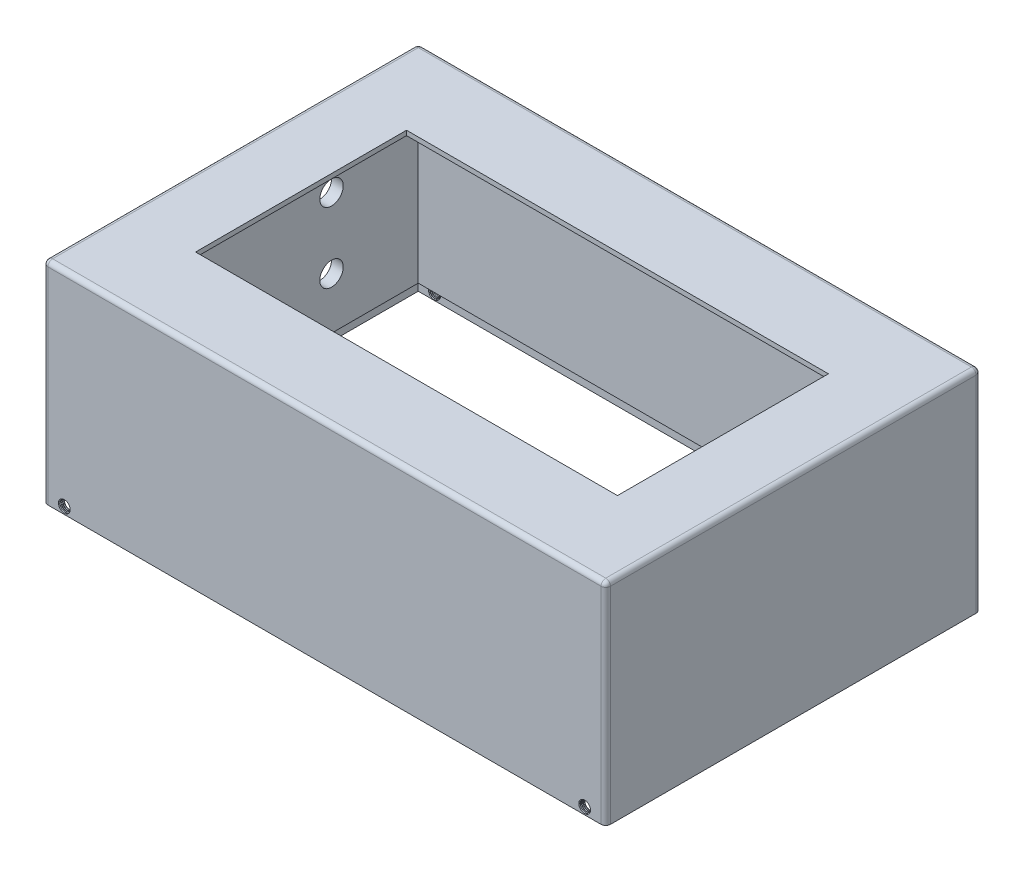
SolidWorks part; units mm, degrees
ref_plane "Front Plane" through (0, 0, 0) normal (0, 0, 1) x (1, 0, 0)
ref_plane "Top Plane" through (0, 0, 0) normal (0, 1, 0) x (1, 0, 0)
ref_plane "Right Plane" through (0, 0, 0) normal (1, 0, 0) x (0, 0, -1)
sketch "Sketch2" plane through (0, 0, 0) normal (0, 1, 0) x (1, 0, 0)
  line L1 (-60, -40) -> (60, -40)
  line L2 (-60, -40) -> (-60, 40)
  line L3 (-60, 40) -> (60, 40)
  line L4 (60, -40) -> (60, 40)
  line L5 (-60, -40) -> (60, 40) construction
  line L6 (-60, 40) -> (60, -40) construction
  point P0 (0, 0)
  dimension "D1" = 80
  dimension "D2" = 120
extrude "Boss-Extrude1" add sketch "Sketch2" along normal blind 50
sketch "Sketch3" plane through (0, 0, 0) normal (0, 1, 0) x (1, 0, 0)
  line L0 (60, -40) -> (60, 40) construction
  line L1 (-57.5, -37.2563) -> (57.5, -37.2563)
  line L2 (-57.5, -37.2563) -> (-57.5, 37.5)
  line L3 (-57.5, 37.5) -> (57.5, 37.5)
  line L4 (57.5, -37.2563) -> (57.5, 37.5)
  line L5 (-60, 40) -> (-60, -40) construction
  line L6 (60, 40) -> (-60, 40) construction
  line L7 (-60, -40) -> (60, -40) construction
  point P0 (0, 0)
  dimension "D1" = 2.5
  dimension "D2" = 2.5
  dimension "D3" = 2.5
  dimension "D4" = 2.7437
extrude "Cut-Extrude4" cut sketch "Sketch3" along normal blind 47.5
fillet "Fillet1" radius 1 8 edges at (-60, 25, -40) (60, 25, -40) (-60, 25, 40) (60, 25, 40) (60, 50, 0) (0, 50, 40) (0, 50, -40) (-60, 50, 0)
sketch "Sketch7" plane through (0, 0, -40) normal (0, 0, -1) x (-1, 0, 0)
  line L0 (-51.5, 10) -> (48.5, 10) construction
  line L1 (-59, 0) -> (59, 0) construction
  line L2 (-59, 49) -> (-59, 0) construction
  text T0 "SIMPLE SOLAR PHONE CHARGER" font "Century Gothic" height in points 18
  dimension "D1" = 10
  dimension "D2" = 100
  dimension "D3" = 7.5
extrude "Boss-Extrude2" add sketch "Sketch7" along normal blind 0.5
sketch "Sketch8" plane through (-60, 0, 0) normal (-1, 0, 0) x (0, 0, 1)
  line L0 (-39, 15) -> (39, 15) construction
  line L1 (-39, 49) -> (-39, 0) construction
  line L2 (39, 0) -> (39, 49) construction
  line L3 (-39, 0) -> (39, 0) construction
  line L4 (39, 49) -> (-39, 49) construction
  line L5 (-44.4082, 26.5) -> (-11.972, 26.5) construction
  line L6 (-10.6538, 11.5) -> (-44.4082, 11.5) construction
  circle A0 centre (-19, 34) radius 2.5
  circle A1 centre (-19, 19) radius 2.5
  text T0 "CHARGING" font "Century Gothic" height in points 8
  text T1 "FULLY CHARGED" font "Century Gothic" height in points 8
  point P19 (-19.3103, 26.5)
  point P20 (0, 0)
  point P21 (-16.5639, 26.5)
  point P22 (0, 0)
  point P23 (0, 0)
  point P24 (0, 0)
  point P25 (-16.5639, 26.5)
  point P26 (0, 0)
  point P27 (0, 0)
  dimension "D2" = 5
  dimension "D3" = 5
  dimension "D4" = 15
  dimension "D7" = 7.5
  dimension "D8" = 20
  dimension "D9" = 20
  dimension "D1" = 15
  dimension "D6" = 7.5
extrude "Cut-Extrude5" cut sketch "Sketch8" against normal blind 2.5 contours A0 | A1
sketch "Sketch9" plane through (-60, 0, 0) normal (-1, 0, 0) x (0, 0, 1)
  line L0 (-39, 28) -> (3.7538, 28) construction
  line L1 (-39, 49) -> (-39, 0) construction
  line L2 (-39, 13) -> (6, 13) construction
  circle A1 centre (-19, 34) radius 2.5 construction
  circle A2 centre (-19, 19) radius 2.5 construction
  text T0 "CHARGING" font "Century Gothic" height in points 8
  text T1 "FULLY CHARGED" font "Century Gothic" height in points 8
  point P7 (0, 0)
  point P8 (0, 0)
  point P9 (-16.6737, 27.1422)
  point P11 (0, 0)
  point P12 (0, 0)
  point P13 (-16.6737, 11.7621)
  point P14 (-3.9898, 27.2439)
  point P15 (3.7538, 27.2439)
  point P16 (-8.6536, 11.7621)
  point P17 (-7.9496, 12.3726)
  point P18 (-6.0137, 11.7621)
  point P19 (1.1139, 11.7621)
  point P20 (0, 0)
  dimension "D1" = 6
  dimension "D2" = 6
  dimension "D3" = 45
  dimension "D4" = 42.7538
extrude "Boss-Extrude3" add sketch "Sketch9" along normal blind 0.5
sketch "Sketch11" plane through (0, 50, 0) normal (0, 1, 0) x (1, 0, 0)
  line L1 (-45, -22.5) -> (45, -22.5)
  line L2 (-45, -22.5) -> (-45, 22.5)
  line L3 (-45, 22.5) -> (45, 22.5)
  line L4 (45, -22.5) -> (45, 22.5)
  line L5 (-45, -22.5) -> (45, 22.5) construction
  line L6 (-45, 22.5) -> (45, -22.5) construction
  point P0 (0, 0)
  dimension "D1" = 90
  dimension "D2" = 45
extrude "Cut-Extrude6" cut sketch "Sketch11" against normal blind 2.5
sketch "Sketch12" plane through (0, 47.5, 0) normal (0, -1, 0) x (1, 0, 0)
  line L0 (-45, 22.5) -> (45, 22.5) construction
  line L1 (-46.5, -24) -> (46.5, -24)
  line L2 (-46.5, -24) -> (-46.5, 24)
  line L3 (-46.5, 24) -> (46.5, 24)
  line L4 (46.5, -24) -> (46.5, 24)
  line L5 (-46.5, -24) -> (46.5, 24) construction
  line L6 (-46.5, 24) -> (46.5, -24) construction
  line L7 (45, -22.5) -> (-45, -22.5) construction
  line L8 (45, 22.5) -> (45, -22.5) construction
  point P0 (0, 0)
  dimension "D1" = 1.5
  dimension "D2" = 1.5
  dimension "D3" = 1.5
extrude "Cut-Extrude7" cut sketch "Sketch12" against normal blind 1.5
sketch "Sketch13" plane through (-60, 0, 0) normal (-1, 0, 0) x (0, 0, 1)
  line L0 (39, 0) -> (39, 49) construction
  line L1 (10, 18.5) -> (24, 18.5)
  line L2 (10, 18.5) -> (10, 12.5)
  line L3 (10, 12.5) -> (24, 12.5)
  line L4 (24, 18.5) -> (24, 12.5)
  line L5 (-39, 0) -> (39, 0) construction
  dimension "D1" = 14
  dimension "D2" = 6
  dimension "D3" = 15
  dimension "D4" = 12.5
extrude "Cut-Extrude8" cut sketch "Sketch13" against normal blind 2.5
sketch "Sketch15" plane through (-60, 0, 0) normal (-1, 0, 0) x (0, 0, 1)
  line L0 (0, 8.5) -> (35, 8.5) construction
  line L1 (-39, 0) -> (39, 0) construction
  text T0 "USB" font "Century Gothic" height in points 8
  dimension "D1" = 8.5
  dimension "D2" = 35
extrude "Boss-Extrude4" add sketch "Sketch15" along normal blind 0.5
sketch "Sketch16" plane through (0, 0, -40) normal (0, 0, -1) x (-1, 0, 0)
  line L0 (60, 49) -> (60, 0) construction
  line L1 (-60, 0) -> (60, 0)
  line L2 (-60, 0) -> (-60, 5)
  line L3 (-60, 5) -> (60, 5)
  line L4 (60, 0) -> (60, 5)
  dimension "D1" = 5
extrude "Cut-Extrude9" cut sketch "Sketch16" against normal blind 80
sketch "Sketch17" plane through (0, 5, 0) normal (0, -1, 0) x (1, 0, 0)
  line L0 (-59, 40) -> (59, 40) construction
  line L1 (-59, -39) -> (59, -39)
  line L2 (-59, -39) -> (-59, 39)
  line L3 (-59, 39) -> (59, 39)
  line L4 (59, -39) -> (59, 39)
  line L5 (-59, -39) -> (59, 39) construction
  line L6 (-59, 39) -> (59, -39) construction
  line L8 (-60, 39) -> (-60, -39) construction
  point P0 (0, 0)
  dimension "D1" = 1
  dimension "D2" = 1
extrude "Cut-Extrude10" cut sketch "Sketch17" against normal blind 3
sketch "Sketch18" plane through (0, 0, -40) normal (0, 0, -1) x (-1, 0, 0)
  line L0 (59, 5) -> (-59, 5) construction
  line L1 (59, 5) -> (59, 49) construction
  line L2 (-59, 49) -> (-59, 5) construction
  circle A0 centre (55.5, 6.5) radius 1.25
  circle A1 centre (-55.5, 6.5) radius 1.25
  dimension "D1" = 2.5
  dimension "D2" = 1.5
  dimension "D3" = 2.5
  dimension "D4" = 1.5
  dimension "D6" = 3.5
  dimension "D5" = 3.5
extrude "Cut-Extrude11" cut sketch "Sketch18" against normal blind 1
sketch "Sketch19" plane through (0, 0, 40) normal (0, 0, 1) x (1, 0, 0)
  line L0 (59, 5) -> (59, 49) construction
  line L1 (-59, 49) -> (-59, 5) construction
  line L2 (-59, 5) -> (59, 5) construction
  circle A0 centre (55.5, 6.5) radius 1.25
  circle A1 centre (-55.5, 6.5) radius 1.25
  dimension "D1" = 2.5
  dimension "D2" = 2.5
  dimension "D4" = 3.5
  dimension "D3" = 3.5
  dimension "D5" = 1.5
  dimension "D6" = 1.5
extrude "Cut-Extrude12" cut sketch "Sketch19" against normal blind 1
thread "Thread1" pitch 0.3175 method extrude profile "Thread Profile1" start angle 0, offset 0, length 0, pitch 0.3175, diameter 2.5
ref_plane "Plane2" through (-56.75, 6.5, 40) normal (0, -1, 0) x (-1, 0, 0)
sketch "Thread Profile1" plane through (-56.75, 6.5, 40) normal (0, -1, 0) x (-1, 0, 0)
  line L0 (0, 0) -> (0, 0.3175) construction
  line L11 (0, 0) -> (0, 0.2778)
  line L12 (0, 0.2778) -> (-0.1719, 0.1786)
  line L13 (-0.1719, 0.1786) -> (-0.1719, 0.0992)
  line L15 (-0.1719, 0.0992) -> (0, 0)
  line L17 (-0.1719, 0.1389) -> (0, 0.1389) construction
  point P2 (0, 0)
  dimension "Pitch" = 0.3175
  dimension "Profile_Angle" = 60
  dimension "Profile_Land" = 0.0794
  dimension "Profile_Height" = 0.1719
thread "Thread2" pitch 0.3175 method extrude profile "Thread Profile2" start angle 0, offset 0, length 0, pitch 0.3175, diameter 2.5
ref_plane "Plane3" through (54.25, 6.5, 40) normal (0, -1, 0) x (-1, 0, 0)
sketch "Thread Profile2" plane through (54.25, 6.5, 40) normal (0, -1, 0) x (-1, 0, 0)
  line L0 (0, 0) -> (0, 0.3175) construction
  line L11 (0, 0) -> (0, 0.2778)
  line L12 (0, 0.2778) -> (-0.1719, 0.1786)
  line L13 (-0.1719, 0.1786) -> (-0.1719, 0.0992)
  line L15 (-0.1719, 0.0992) -> (0, 0)
  line L17 (-0.1719, 0.1389) -> (0, 0.1389) construction
  point P2 (0, 0)
  dimension "Pitch" = 0.3175
  dimension "Profile_Angle" = 60
  dimension "Profile_Land" = 0.0794
  dimension "Profile_Height" = 0.1719
thread "Thread3" pitch 0.3175 method extrude profile "Thread Profile3" start angle 0, offset 0, length 0, pitch 0.3175, diameter 2.5
ref_plane "Plane4" through (-54.25, 6.5, -40) normal (0, -1, 0) x (1, 0, 0)
sketch "Thread Profile3" plane through (-54.25, 6.5, -40) normal (0, -1, 0) x (1, 0, 0)
  line L0 (0, 0) -> (0, 0.3175) construction
  line L11 (0, 0) -> (0, 0.2778)
  line L12 (0, 0.2778) -> (-0.1719, 0.1786)
  line L13 (-0.1719, 0.1786) -> (-0.1719, 0.0992)
  line L15 (-0.1719, 0.0992) -> (0, 0)
  line L17 (-0.1719, 0.1389) -> (0, 0.1389) construction
  point P2 (0, 0)
  dimension "Pitch" = 0.3175
  dimension "Profile_Angle" = 60
  dimension "Profile_Land" = 0.0794
  dimension "Profile_Height" = 0.1719
thread "Thread4" pitch 0.3175 method extrude profile "Thread Profile4" start angle 6, offset 0, length 0, pitch 0.3175, diameter 2.5
ref_plane "Plane5" through (56.7432, 6.6307, -40) normal (0.1045, -0.9945, 0) x (0.9945, 0.1045, 0)
sketch "Thread Profile4" plane through (56.7432, 6.6307, -40) normal (0.1045, -0.9945, 0) x (0.9945, 0.1045, 0)
  line L0 (0, 0) -> (0, 0.3175) construction
  line L11 (0, 0) -> (0, 0.2778)
  line L12 (0, 0.2778) -> (-0.1719, 0.1786)
  line L13 (-0.1719, 0.1786) -> (-0.1719, 0.0992)
  line L15 (-0.1719, 0.0992) -> (0, 0)
  line L17 (-0.1719, 0.1389) -> (0, 0.1389) construction
  point P2 (0, 0)
  dimension "Pitch" = 0.3175
  dimension "Profile_Angle" = 60
  dimension "Profile_Land" = 0.0794
  dimension "Profile_Height" = 0.1719
